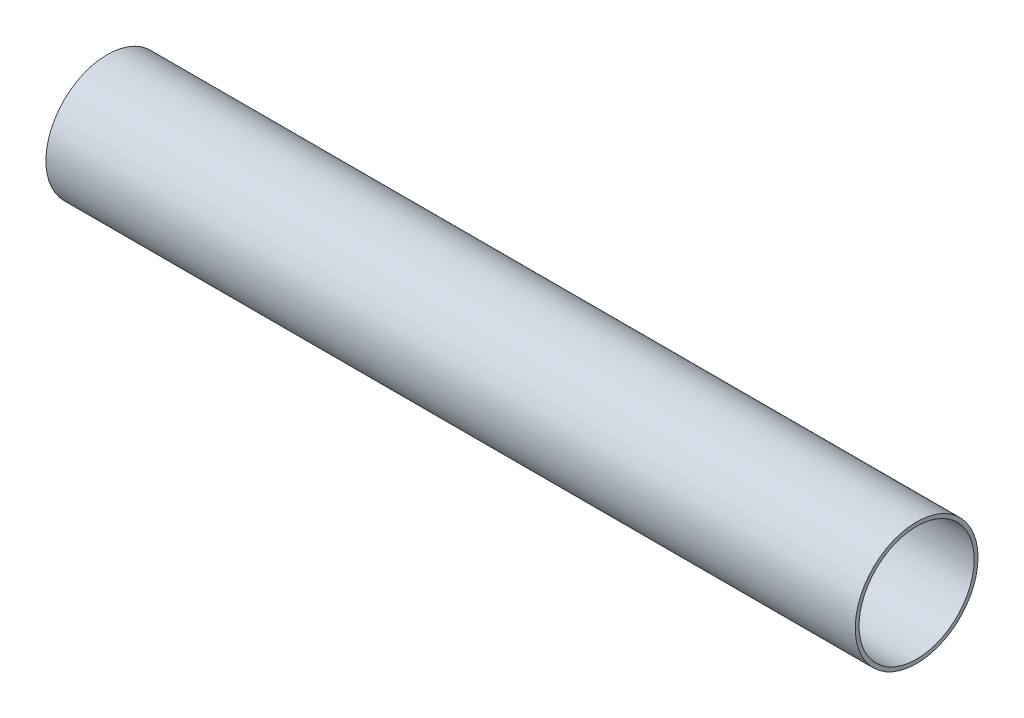
SolidWorks part; units mm, degrees
other "Exploded View1" [suppressed]
other "Explode Step1" [suppressed]
other "Explode Line1"
other "Explode Step2" [suppressed]
other "Explode Line1"
material "PC High Viscosity"
ref_plane "Front Plane" through (0, 0, 0) normal (0, 0, 1) x (1, 0, 0)
ref_plane "Top Plane" through (0, 0, 0) normal (0, 1, 0) x (1, 0, 0)
ref_plane "Right Plane" through (0, 0, 0) normal (1, 0, 0) x (0, 0, -1)
sketch "Sketch1" plane through (0, 0, 0) normal (1, 0, 0) x (0, 0, -1)
  circle A0 centre (0, 0) radius 25.4
  dimension "D1" = 50.8
extrude "Extrude-Thin1" add sketch "Sketch1" along normal mid plane 334.899 thin thin type one direction reverse wall 1.5875
equation "\"D2@Sketch2\"=21mm"
